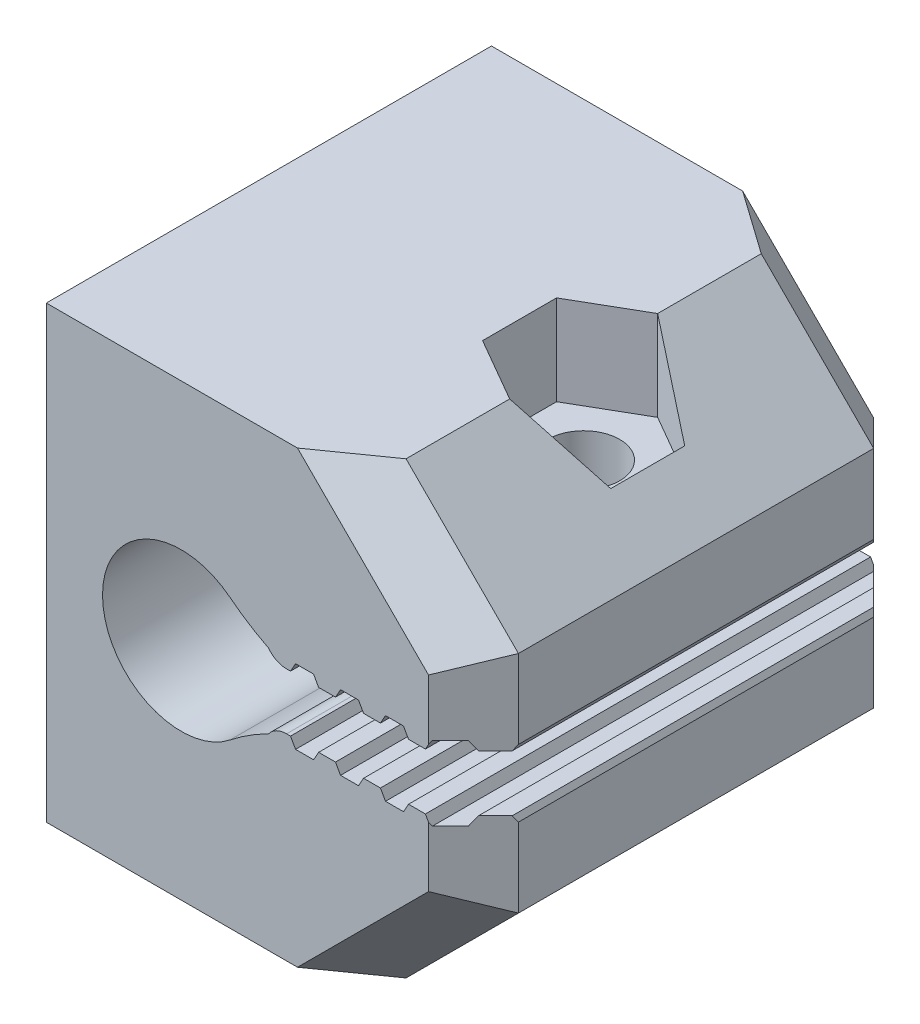
SolidWorks part; units mm, degrees
ref_plane "Front Plane" through (0, 0, 0) normal (0, 0, 1) x (1, 0, 0)
ref_plane "Top Plane" through (0, 0, 0) normal (0, 1, 0) x (1, 0, 0)
ref_plane "Right Plane" through (0, 0, 0) normal (1, 0, 0) x (0, 0, -1)
sketch "Sketch1" plane through (0, 0, 0) normal (0, 0, 1) x (1, 0, 0)
  line L0 (18.8617, 11.25) -> (18.1117, 11.25)
  line L1 (0, 0) -> (19, 0)
  line L2 (0, 0) -> (0, 20)
  line L3 (0, 20) -> (19, 20)
  line L4 (19, 0) -> (19, 8.5041)
  line L5 (18.8617, 8.75) -> (18.1117, 8.75)
  line L6 (-20.2431, 10) -> (34.5163, 10) construction
  line L7 (19, 11.4959) -> (19, 20)
  line L8 (-9.4211, 11.65) -> (29.5037, 11.65) construction
  line L9 (17.0867, 8.35) -> (17.8867, 8.35)
  line L10 (28.8037, 8.35) -> (-6.7273, 8.35) construction
  line L11 (9.0867, 11.65) -> (9.8867, 11.65)
  line L12 (9.8867, 11.65) -> (10.1117, 11.25)
  line L13 (9.4867, 12.3238) -> (9.4867, 10.3848) construction
  line L14 (11.8867, 11.65) -> (12.1117, 11.25)
  line L15 (11.0867, 11.65) -> (11.8867, 11.65)
  line L16 (10.8617, 11.25) -> (11.0867, 11.65)
  line L17 (13.8867, 11.65) -> (14.1117, 11.25)
  line L18 (13.0867, 11.65) -> (13.8867, 11.65)
  line L19 (12.8617, 11.25) -> (13.0867, 11.65)
  line L20 (15.8867, 11.65) -> (16.1117, 11.25)
  line L21 (15.0867, 11.65) -> (15.8867, 11.65)
  line L22 (14.8617, 11.25) -> (15.0867, 11.65)
  line L23 (17.8867, 11.65) -> (18.1117, 11.25)
  line L24 (17.0867, 11.65) -> (17.8867, 11.65)
  line L25 (16.8617, 11.25) -> (17.0867, 11.65)
  line L26 (16.8617, 11.25) -> (16.1117, 11.25)
  line L27 (14.8617, 11.25) -> (14.1117, 11.25)
  line L28 (18.8617, 11.25) -> (19, 11.4959)
  line L29 (19.8867, 11.65) -> (20.1117, 11.25) [skipped]
  line L30 (19.0867, 11.65) -> (19.8867, 11.65) [skipped]
  line L31 (12.8617, 11.25) -> (12.1117, 11.25)
  line L32 (10.8617, 11.25) -> (10.1117, 11.25)
  line L33 (15.0867, 8.35) -> (15.8867, 8.35)
  line L34 (13.0867, 8.35) -> (13.8867, 8.35)
  line L35 (11.0867, 8.35) -> (11.8867, 8.35)
  line L36 (9.0867, 8.35) -> (9.8867, 8.35)
  line L37 (18.8617, 8.75) -> (19, 8.5041)
  line L38 (17.8867, 8.35) -> (18.1117, 8.75)
  line L39 (16.8617, 8.75) -> (17.0867, 8.35)
  line L40 (15.8867, 8.35) -> (16.1117, 8.75)
  line L41 (14.8617, 8.75) -> (15.0867, 8.35)
  line L42 (12.8617, 8.75) -> (13.0867, 8.35)
  line L43 (13.8867, 8.35) -> (14.1117, 8.75)
  line L44 (10.8617, 8.75) -> (11.0867, 8.35)
  line L45 (11.8867, 8.35) -> (12.1117, 8.75)
  line L46 (9.8867, 8.35) -> (10.1117, 8.75)
  line L47 (10.8617, 8.75) -> (10.1117, 8.75)
  line L48 (12.8617, 8.75) -> (12.1117, 8.75)
  line L49 (14.8617, 8.75) -> (14.1117, 8.75)
  line L50 (16.8617, 8.75) -> (16.1117, 8.75)
  arc A0 (9.0867, 11.65) -> (9.0867, 8.35) centre (6, 10) ccw
  dimension "D3" = 6
  dimension "D5" = 7
  dimension "D9" = 0.225
  dimension "D1" = 20
  dimension "D2" = 19
  dimension "D6" = 2.5
  dimension "D7" = 3.3
  dimension "D10" = 0.8
  dimension "D12" = 2
  dimension "D13" = 0.1383
  dimension "D14" = 0.2459
  dimension "D11" = 6
extrude "Boss-Extrude1" add sketch "Sketch1" along normal blind 19.8
fillet "Fillet1" radius 10 2 edges at (9.0867, 8.35, 9.9) (9.0867, 11.65, 9.9)
fillet "Fillet2" radius 1 2 edges at (10.1117, 8.75, 9.9) (10.1117, 11.25, 9.9)
chamfer "Chamfer1" distance 5 angle 45 2 edges at (19, 0, 9.9) (19, 20, 9.9)
sketch "Sketch2" plane through (0, 0, 0) normal (0, -1, 0) x (1, 0, 0)
  line L0 (0, 19.8) -> (14, 19.8) construction
  line L1 (0, 19.8) -> (0, 0) construction
  circle A0 centre (14, 9.9) radius 1.6
  dimension "D1" = 3.2
  dimension "D2" = 9.9
  dimension "D3" = 14
extrude "Cut-Extrude1" cut sketch "Sketch2" against normal up to surface (20 mm away) up to face at (7, 20, 9.9)
sketch "Sketch3" plane through (0, 0, 0) normal (0, -1, 0) x (1, 0, 0)
  circle A0 centre (14, 9.9) radius 3
  dimension "D1" = 6
extrude "Cut-Extrude2" cut sketch "Sketch3" against normal blind 4
sketch "Sketch4" plane through (0, 20, 0) normal (0, 1, 0) x (1, 0, 0)
  line L0 (19, 0) -> (19, -19.8) construction
  line L1 (11.15, -8.2546) -> (11.15, -11.5454)
  line L2 (11.15, -11.5454) -> (14, -13.1909)
  line L3 (14, -13.1909) -> (16.85, -11.5454)
  line L4 (16.85, -11.5454) -> (16.85, -8.2546)
  line L5 (16.85, -8.2546) -> (14, -6.6091)
  line L6 (14, -6.6091) -> (11.15, -8.2546)
  circle A0 centre (14, -9.9) radius 2.85 construction
  dimension "D1" = 5.7
extrude "Cut-Extrude3" cut sketch "Sketch4" against normal blind 4
chamfer "Chamfer2" distance 2 angle 45 8 edges at (16.5, 2.5, 0) (19, 6.752, 0) (16.5, 17.5, 0) (19, 13.248, 0) (16.5, 17.5, 19.8) (19, 13.248, 19.8) (19, 6.752, 19.8) (16.5, 2.5, 19.8)
